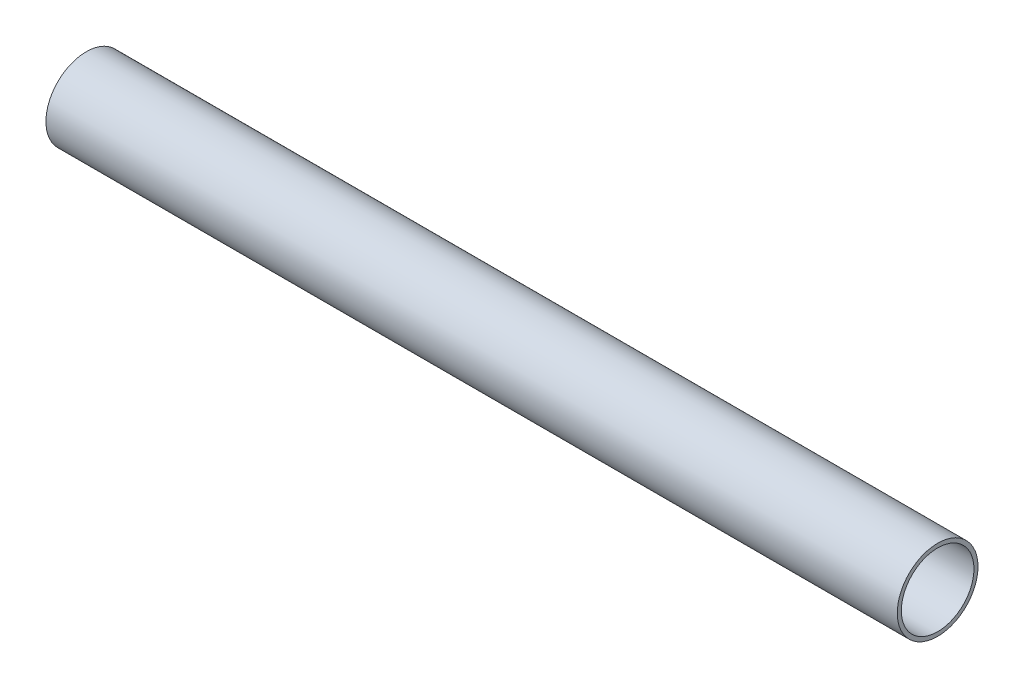
SolidWorks part; units mm, degrees
material "PC High Viscosity"
ref_plane "Front Plane" through (0, 0, 0) normal (0, 0, 1) x (1, 0, 0)
ref_plane "Top Plane" through (0, 0, 0) normal (0, 1, 0) x (1, 0, 0)
ref_plane "Right Plane" through (0, 0, 0) normal (1, 0, 0) x (0, 0, -1)
sketch "Sketch1" plane through (0, 0, 0) normal (1, 0, 0) x (0, 0, -1)
  circle A0 centre (0, 0) radius 15.875
  dimension "D1" = 31.75
extrude "Extrude-Thin1" add sketch "Sketch1" along normal mid plane 334.899 thin thin type one direction reverse wall 1.5875
equation "\"D2@Sketch2\"=21mm"
